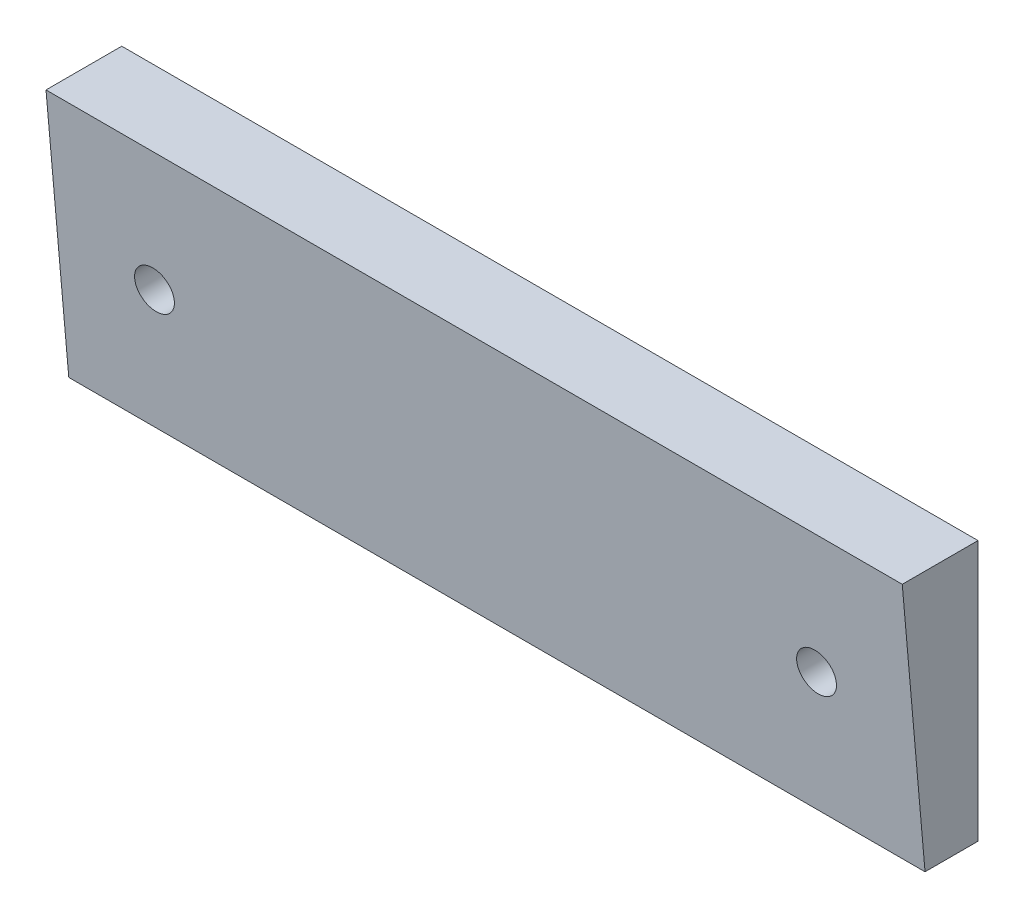
SolidWorks part; units mm, degrees
ref_plane "Front Plane" through (0, 0, 0) normal (0, 0, 1) x (1, 0, 0)
ref_plane "Top Plane" through (0, 0, 0) normal (0, 1, 0) x (1, 0, 0)
ref_plane "Right Plane" through (0, 0, 0) normal (1, 0, 0) x (0, 0, -1)
ref_plane "PL_Ym48_5" through (-48.5, 0, 0) normal (1, 0, 0) x (0, 0, -1)
sketch "SK_Body" plane through (-48.5, 0, 0) normal (1, 0, 0) x (0, 0, -1)
  line L0 (0, -19.5) -> (-6, -19.5)
  line L1 (-6, -19.5) -> (-8.5809, 10)
  line L2 (-8.5809, 10) -> (0, 10)
  line L3 (0, 10) -> (0, -19.5)
  dimension "D1" = 19.5
  dimension "D2" = 6
  dimension "D3" = 19.5
  dimension "D4" = 8.5809
  dimension "D5" = 10
  dimension "D6" = 10
extrude "EX_Body" add sketch "SK_Body" along normal blind 97
sketch "SK_Inserts_M3" plane through (0, 0, 0) normal (0, 0, 1) x (1, 0, 0)
  circle A0 centre (15, 0) radius 2
  circle A1 centre (-15, 0) radius 2
  dimension "D2" = 4
  dimension "D4" = 4
  dimension "D1" = 15
  dimension "D3" = 15
extrude "CUT_Inserts_M3" cut sketch "SK_Inserts_M3" along normal blind 5.7
sketch "SK_VESA_M4" plane through (0, 0, 0) normal (0, 0, 1) x (1, 0, 0)
  circle A0 centre (37.5, -4.75) radius 2.25
  circle A1 centre (-37.5, -4.75) radius 2.25
  dimension "D3" = 4.5
  dimension "D6" = 4.5
  dimension "D1" = 37.5
  dimension "D2" = 4.75
  dimension "D4" = 37.5
  dimension "D5" = 4.75
extrude "CUT_VESA_M4" cut sketch "SK_VESA_M4" along normal blind 12
ref_axis "AX_X" through (0, 0, -0.8834) along (0, 0, 1)
ref_axis "AX_Y" through (53.35, 0, 0) along (-1, 0, 0)
ref_axis "AX_Z" through (0, 11.475, 0) along (0, -1, 0)
sketch "SK_F_IF_OAK" plane through (0, 0, 0) normal (1, 0, 0) x (0, 0, -1)
  line L0 (-7.706, 0) -> (-17.668, -0.8716) construction
  dimension "D1" = 7.706
  dimension "D2" = 17.668
  dimension "D3" = 0.8716
